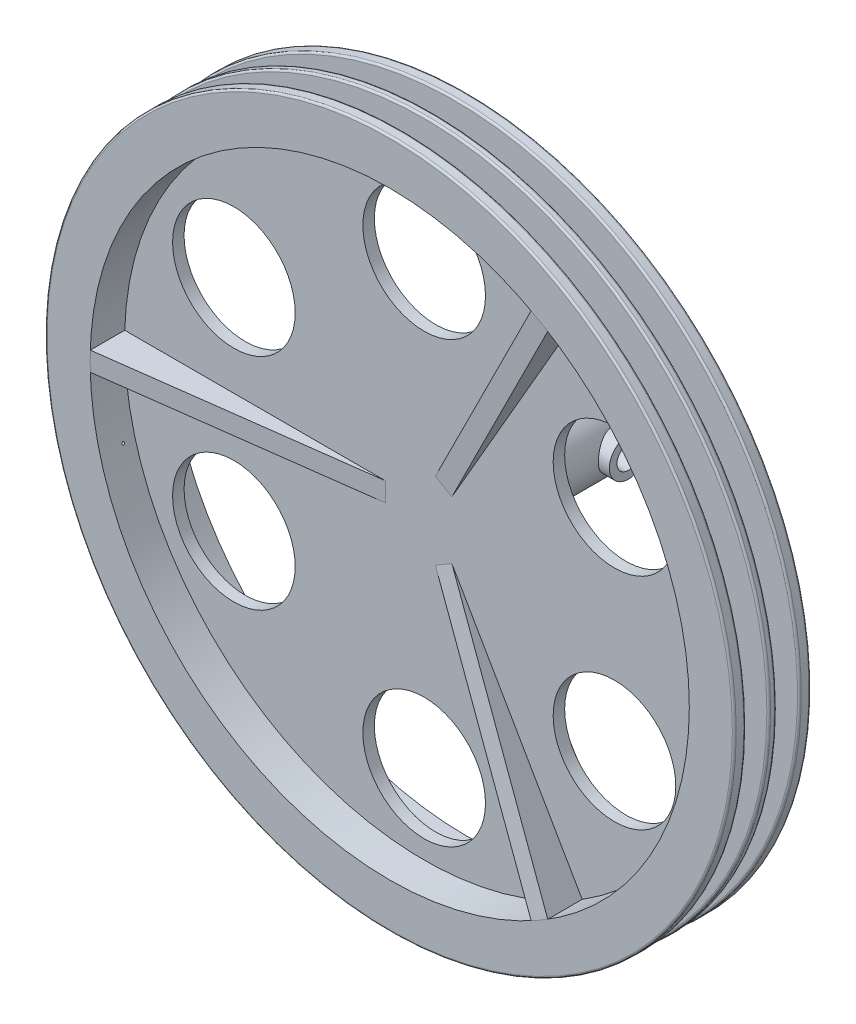
SolidWorks part; units mm, degrees
other "标注1"
sketch "草图4" plane through (-10.9, 14.2335, 40) normal (-0.0377, 0.1644, 0.9857) x (0.9979, 0.0583, 0.0285)
other "标注2"
sketch "草图48" plane through (92.5, 92.5, 0) normal (0.615, 0.2775, -0.7381) x (0.7255, -0.5659, 0.3918)
ref_plane "前视基准面" through (0, 0, 0) normal (0, 0, 1) x (1, 0, 0)
ref_plane "上视基准面" through (0, 0, 0) normal (0, 1, 0) x (1, 0, 0)
ref_plane "右视基准面" through (0, 0, 0) normal (1, 0, 0) x (0, 0, -1)
sketch "草图2" plane through (0, 0, 0) normal (0, 0, 1) x (1, 0, 0)
  circle A0 centre (0, 0) radius 10.9
  circle A1 centre (0, 0) radius 9
  dimension "D1" = 21.8
  dimension "D2" = 18
extrude "凸台-拉伸1" add sketch "草图2" along normal blind 42.2
sketch "草图14" plane through (0, 0, 42.2) normal (0, 0, 1) x (1, 0, 0)
  circle A0 centre (0, 0) radius 80
  dimension "D1" = 160
extrude "凸台-拉伸4" add sketch "草图14" along normal blind 3
sketch "草图15" plane through (0, 0, 42.2) normal (0, 0, -1) x (-1, 0, 0)
  circle A0 centre (0, 0) radius 78.25
  circle A1 centre (0, 0) radius 80
  dimension "D1" = 156.5
  dimension "D2" = 160
extrude "凸台-拉伸5" add sketch "草图15" along normal blind 5
sketch "草图16" plane through (0, 0, 45.2) normal (0, 0, 1) x (1, 0, 0)
  circle A0 centre (0, 0) radius 78.25
  circle A1 centre (0, 0) radius 80
  dimension "D1" = 156.5
  dimension "D2" = 160
extrude "凸台-拉伸6" add sketch "草图16" along normal blind 6
sketch "草图17" plane through (0, 0, 37.2) normal (0, 0, -1) x (-1, 0, 0)
  circle A0 centre (0, 0) radius 90
  circle A1 centre (0, 0) radius 78.25
  dimension "D1" = 180
extrude "凸台-拉伸7" add sketch "草图17" along normal blind 3
sketch "草图19" plane through (0, 0, 42.2) normal (0, 0, -1) x (-1, 0, 0)
  circle A0 centre (0, 57.3862) radius 16.01
  circle A1 centre (49.6979, 28.6931) radius 16.01
  circle A2 centre (49.6979, -28.6931) radius 16.01
  circle A3 centre (0, -57.3862) radius 16.01
  circle A4 centre (-49.6979, -28.6931) radius 16.01
  circle A5 centre (-49.6979, 28.6931) radius 16.01
  dimension "D1" = 32.02
  dimension "D2" = 6
extrude "切除-拉伸3" cut sketch "草图19" against normal through all
sketch "草图21" plane through (0, 0, 0) normal (0, 1, 0) x (1, 0, 0)
sketch "草图23" plane through (0, 0, 51.2) normal (0, 0, 1) x (1, 0, 0)
  circle A0 centre (0, 0) radius 90
  circle A1 centre (0, 0) radius 78.25
  dimension "D1" = 180
extrude "凸台-拉伸9" add sketch "草图23" along normal blind 3
sketch "草图28" plane through (0, 0, 0) normal (0, 0, -1) x (-1, 0, 0)
  line L0 (-2.75, 9.1419) -> (-2.75, 7.8)
  line L1 (-2.75, 7.8) -> (2.75, 7.8)
  line L2 (2.75, 7.8) -> (2.75, 9.1419)
  line L3 (0, 15.3626) -> (0, -13.2314) construction
  line L4 (-2.75, 9.1419) -> (2.75, 9.1419)
  circle A1 centre (0, 0) radius 9 construction
  dimension "D1" = 5.5
  dimension "D2" = 7.8
extrude "凸台-拉伸10" add sketch "草图28" against normal blind 6
sketch "草图32" plane through (0, 0, 0) normal (1, 0, 0) x (0, 0, -1)
  line L0 (-68.3492, 0) -> (2.9423, 0)
  line L1 (-53.3082, 15) -> (1.5135, 15)
  line L2 (31.46, 0) -> (-31.46, 0) construction
  line L3 (-15.6, 20.5091) -> (-15.6, -21.9034)
  line L4 (0, -10.9) -> (0, 10.9) construction
  line L5 (0, -15) -> (-68.3492, -15)
  dimension "D1" = 15.6
  dimension "D2" = 15
  dimension "D3" = 15
curve "曲线1"
curve "曲线2"
sketch "草图32<3>" plane through (0, 0, 0) normal (1, 0, 0) x (0, 0, -1) same geometry as "草图32"
ref_plane "基准面1" through (0, 0, 0) normal (-0.866, -0.5, 0) x (0, 0, -1)
sketch "草图35" plane through (0, 0, 0) normal (-0.866, -0.5, 0) x (0, 0, -1)
  line L0 (-34.2, 78.25) -> (-35.4224, 10.9)
  line L1 (0, 10.9) -> (-42.2, 10.9) construction
rib "筋38" sketch "草图35" sketch "草图35" thickness 5 extrusion direction parallel to sketch draft on no parameters "D1"=5
pattern_circular "阵列(圆周)4" count 3 over 360 about axis through (0, 0, 34.2) along (0, 0, -1) of "筋38"
sketch "草图36" plane through (0, 0, 0) normal (-0.866, -0.5, 0) x (0, 0, -1)
  line L0 (-54.2, 78.25) -> (-45.2, 10.1553)
  line L2 (-45.2, 78.25) -> (-45.2, -78.25) construction
rib "筋43" sketch "草图36" sketch "草图36" thickness 5 extrusion direction parallel to sketch draft on no parameters "D1"=5
pattern_circular "阵列(圆周)5" count 3 over 360 about axis through (0, 0, 54.2) along (0, 0, 1) of "筋43"
fillet "圆角1" radius 0.5 4 edges at (-90, 0, 37.2) (-90, 0, 34.2) (90, 0, 54.2) (90, 0, 51.2)
curve "曲线4"
sketch "草图32<5>" plane through (0, 0, 0) normal (1, 0, 0) x (0, 0, -1) same geometry as "草图32"
ref_plane "基准面2" through (0, 0, 44.2) normal (0, 0, 1) x (1, 0, 0)
ref_plane "基准面3" through (-13.75, 0, 0) normal (-1, 0, 0) x (0, 0, 1)
sketch "草图47" plane through (-13.75, 0, 0) normal (-1, 0, 0) x (0, 0, 1)
  line L0 (42.2, 0) -> (0, 0) construction
  line L1 (0, 10.9) -> (0, -10.9) construction
  circle A0 centre (15.6, 0) radius 5
  dimension "D1" = 10
  dimension "D2" = 15.6
sketch "草图49" plane through (-13.75, 0, 0) normal (-1, 0, 0) x (0, 0, 1)
  line L0 (15.6, -10.9) -> (15.6, 10.9) construction
  circle A0 centre (15.6, 0) radius 3
  dimension "D1" = 6
sketch "草图52" plane through (0, 0, 44.2) normal (0, 0, 1) x (1, 0, 0)
  circle A0 centre (0, 0) radius 80
  circle A1 centre (0, 0) radius 90
  dimension "D1" = 180
extrude "凸台-拉伸14" add sketch "草图52" along normal mid plane 2
fillet "圆角3" radius 0.5 2 edges at (90, 0, 45.2) (90, 0, 43.2)
sketch "草图59" plane through (0, 0, 0) normal (1, 0, 0) x (0, 0, -1)
  line L0 (-15.6, 0) -> (-10.6, 0)
  line L1 (-15.6, -10.9) -> (-15.6, 10.9) construction
  line L2 (-42.2, 0) -> (0, 0) construction
  line L3 (-10.6, 0) -> (-5.6, 0)
  circle A2 centre (-15.6, 0) radius 5 construction
  circle A3 centre (-5.6, 0) radius 5
  circle A5 centre (-5.6, 0) radius 3
sketch "草图60" plane through (-13.75, 0, 0) normal (-1, 0, 0) x (0, 0, 1)
  line L0 (15.6, 0) -> (10.6, 0)
  line L1 (42.2, 0) -> (0, 0) construction
  circle A0 centre (15.6, 0) radius 5 construction
extrude "切除-拉伸7" cut sketch "草图59" against normal blind 15 and the other way blind 15 contours A5
ref_plane "基准面4" through (-10.1553, 2.5, 45.2) normal (0, 1, 0) x (1, 0, 0)
sketch "草图71" plane through (0, 0, 0) normal (0, 0, -1) x (-1, 0, 0)
  line L0 (-2.75, 8.5696) -> (-2.75, 7.8)
  line L1 (-2.75, 7.8) -> (2.75, 7.8)
  line L2 (2.75, 7.8) -> (2.75, 8.5696)
  circle A0 centre (0, 0) radius 10.9
  arc A1 (-2.75, 8.5696) -> (2.75, 8.5696) centre (0, 0) ccw
extrude "凸台-拉伸17" add sketch "草图71" along normal blind 6.6
sketch "草图72" plane through (-13.75, 0, 0) normal (-1, 0, 0) x (0, 0, 1)
  circle A0 centre (5.6, 0) radius 5
extrude "凸台-拉伸19" add sketch "草图72" against normal blind 27.5 contours A0
sketch "草图76" plane through (0, 0, -6.6) normal (0, 0, -1) x (-1, 0, 0)
  line L0 (-2.75, 8.5696) -> (-2.75, 7.8)
  line L1 (-2.75, 7.8) -> (2.75, 7.8)
  line L2 (2.75, 7.8) -> (2.75, 8.5696)
  arc A1 (-2.75, 8.5696) -> (2.75, 8.5696) centre (0, 0) ccw
extrude "切除-拉伸8" cut sketch "草图76" against normal blind 20
sketch "草图77" plane through (-13.75, 0, 0) normal (-1, 0, 0) x (0, 0, 1)
  circle A0 centre (5.6, 0) radius 3
extrude "切除-拉伸9" cut sketch "草图77" against normal blind 27.5
sketch "草图80" plane through (0, 0, 45.2) normal (0, 0, 1) x (1, 0, 0)
  line L0 (0, 0) -> (-49.6979, -28.6931)
  line L1 (0, 0) -> (-55.4308, -14.8526)
  line L2 (-55.4308, -14.8526) -> (-75.5837, -20.2526)
  line L3 (-75.5837, -20.2526) -> (75.5837, 20.2526)
  line L4 (-75.5837, -20.2526) -> (-71.8393, -19.2493)
  line L5 (-71.8393, -19.2493) -> (-73.3291, -13.6892)
  line L6 (-73.3291, -13.6892) -> (-70.5161, -24.1877)
  arc A0 (-49.6979, -28.6931) -> (-55.4308, -14.8526) centre (0, 0) cw
  arc A1 (-78.25, 0) -> (39.125, -67.7665) centre (0, 0) ccw construction
  arc A2 (39.125, -67.7665) -> (39.125, 67.7665) centre (0, 0) ccw construction
ref_plane "基准面5" through (0, 0, 0) normal (-0.9659, -0.2588, 0) x (0, 0, 1)
ref_plane "基准面6" through (-86.9333, -23.2937, 0) normal (-0.9659, -0.2588, 0) x (0, 0, 1)
ref_plane "基准面7" through (86.9333, 23.2937, 0) normal (-0.9659, -0.2588, 0) x (0, 0, 1)
sketch "草图82" plane through (-86.9333, -23.2937, 0) normal (-0.9659, -0.2588, 0) x (0, 0, 1)
  line L0 (45.2, 0) -> (51.2, 0)
  line L1 (45.2, -14.8526) -> (45.2, 0) construction
  line L2 (54.2, 0) -> (45.2, 0) construction
  line L3 (44.7, 0) -> (43.7, 0) construction
  line L4 (43.2, 0) -> (37.2, 0)
  line L5 (43.2, 80) -> (43.2, -80) construction
  line L6 (42.2, 0) -> (-6.6, 0) construction
  line L7 (43.2, 0) -> (37.2, 0) construction
  circle A0 centre (40.2, 0) radius 0.35
  circle A1 centre (48.2, 0) radius 0.35
extrude "切除-拉伸10" cut sketch "草图82" against normal blind 20 contours A1 | A0
sketch "草图83" plane through (86.9333, 23.2937, 0) normal (-0.9659, -0.2588, 0) x (0, 0, 1)
  circle A0 centre (40.2, 0) radius 0.35
  circle A1 centre (48.2, 0) radius 0.35
extrude "切除-拉伸11" cut sketch "草图83" along normal blind 20
